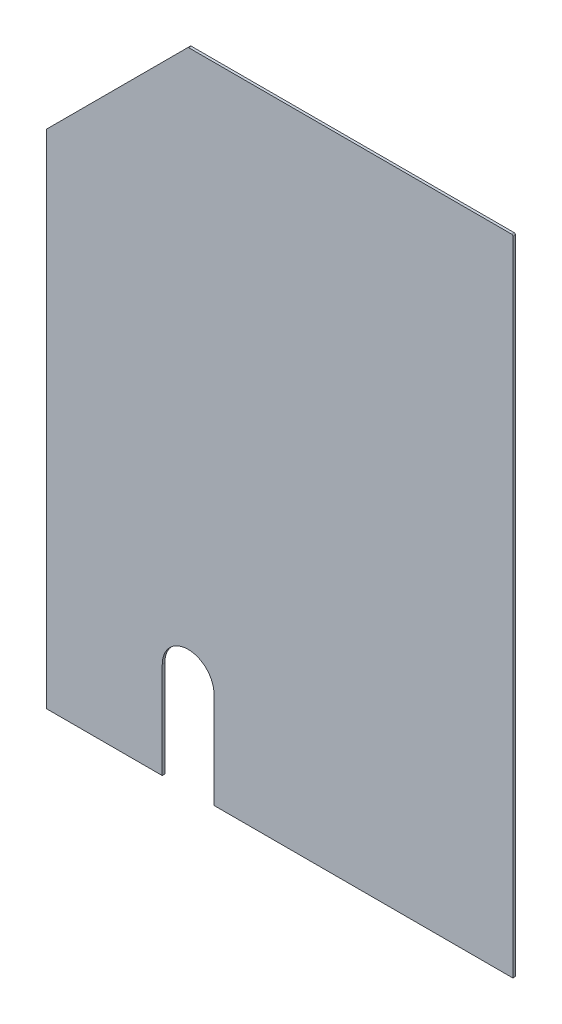
SolidWorks part; units mm, degrees
material "AISI 1020"
ref_plane "Спереди" through (0, 0, 0) normal (0, 0, 1) x (1, 0, 0)
ref_plane "Сверху" through (0, 0, 0) normal (0, 1, 0) x (1, 0, 0)
ref_plane "Справа" through (0, 0, 0) normal (1, 0, 0) x (0, 0, -1)
sketch "Эскиз1" plane through (0, 0, 0) normal (0, 0, 1) x (1, 0, 0)
  line L0 (-270.0767, 290.5011) -> (-270.0767, -15.2562) construction
  line L1 (-188.2964, 372.5921) -> (-269.857, 291.0314) construction
  line L2 (-0.75, 372.8118) -> (-187.766, 372.8118) construction
  line L3 (0, -15.2562) -> (0, 372.0618) construction
  line L4 (-270.0767, 290.5011) -> (-270.0767, 0)
  line L5 (-188.2964, 372.5921) -> (-269.857, 291.0314)
  line L6 (-0.75, 372.8118) -> (-187.766, 372.8118)
  line L7 (0, 0) -> (0, 372.0618)
  line L8 (-188.0767, 55.8118) -> (-188.0767, -40) construction
  line L9 (-173.0767, 55.8118) -> (-173.0767, 0)
  line L10 (-203.0767, 55.8118) -> (-203.0767, 0)
  line L11 (-270.0767, 0) -> (-203.0767, 0)
  line L12 (824.9034, 0) -> (-265.0767, 0) construction
  line L13 (-173.0767, 0) -> (0, 0)
  arc A0 (-269.857, 291.0314) -> (-270.0767, 290.5011) centre (-269.3267, 290.5011) ccw construction
  arc A1 (-187.766, 372.8118) -> (-188.2964, 372.5921) centre (-187.766, 372.0618) ccw construction
  arc A2 (0, 372.0618) -> (-0.75, 372.8118) centre (-0.75, 372.0618) ccw construction
  arc A3 (-269.857, 291.0314) -> (-270.0767, 290.5011) centre (-269.3267, 290.5011) ccw
  arc A4 (-187.766, 372.8118) -> (-188.2964, 372.5921) centre (-187.766, 372.0618) ccw
  arc A5 (0, 372.0618) -> (-0.75, 372.8118) centre (-0.75, 372.0618) ccw
  arc A6 (-173.0767, 55.8118) -> (-203.0767, 55.8118) centre (-188.0767, 55.8118) ccw
  circle A8 centre (-188.0767, 55.8118) radius 11.75 construction
  point P9 (-188.0767, 7.9059)
  dimension "D1" = 30
base flange "Базовая кромка1" sketch "Эскиз1" thickness 1.5 reverse thickness direction no parameters "D1"=0.75
sketch "Сгиб-Линии1" [suppressed] plane through (0, 0, 0) normal (0, 1, 0) x (1, 0, 0)
sketch "Граничная рамка1" [suppressed] plane through (0, 0, 0) normal (0, 1, 0) x (1, 0, 0)
sheet metal parameters "Листовой металл3" thickness 1.5 parameters "D1"=0.75
flat pattern "Развертка3" [suppressed]
sketch "Сгиб-Линии2" plane through (0, 0, 0) normal (0, 1, 0) x (1, 0, 0)
sketch3d "Граничная рамка2" [suppressed]
  line L0 (269.3267, 82.3107, 0) -> (269.3267, -290.5011, 0) construction
  line L1 (-0.75, 82.3107, 0) -> (-0.75, -290.5011, 0) construction
  line L2 (269.3267, 82.3107, 0) -> (-0.75, 82.3107, 0) construction
  line L3 (269.3267, -290.5011, 0) -> (-0.75, -290.5011, 0) construction
